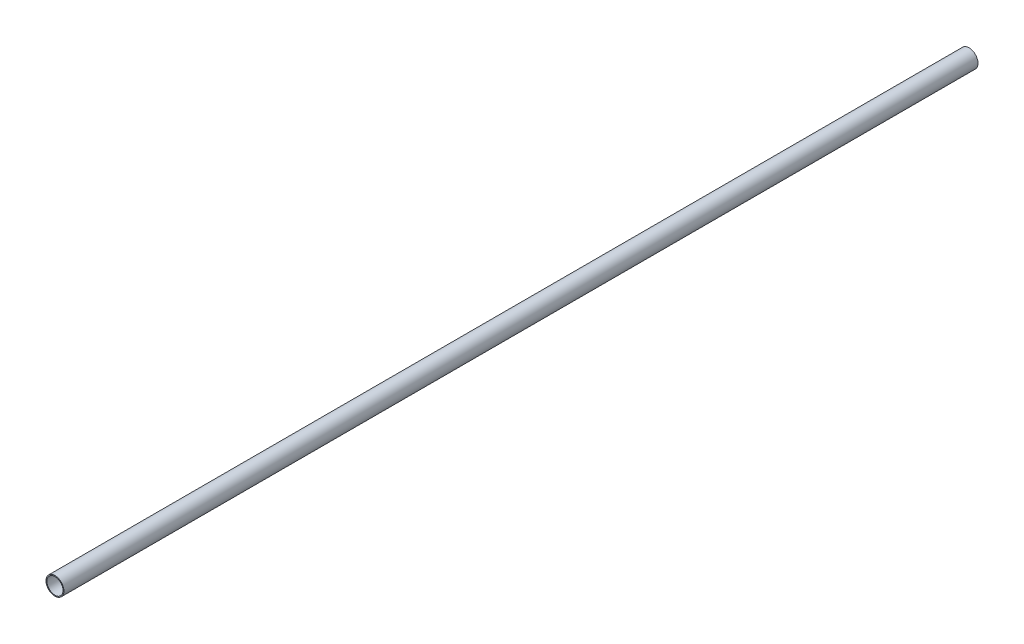
SolidWorks part; units mm, degrees
material "6061 Alloy"
ref_plane "Front Plane" through (0, 0, 0) normal (0, 0, 1) x (1, 0, 0)
ref_plane "Top Plane" through (0, 0, 0) normal (0, 1, 0) x (1, 0, 0)
ref_plane "Right Plane" through (0, 0, 0) normal (1, 0, 0) x (0, 0, -1)
sketch "Sketch1" plane through (0, 0, 0) normal (0, 0, 1) x (1, 0, 0)
  circle A0 centre (0, 0) radius 3.175
  circle A1 centre (0, 0) radius 2.8575
  dimension "D1" = 6.35
  dimension "D2" = 0.3175
extrude "Boss-Extrude1" add sketch "Sketch1" along normal blind 311.15 and the other way blind 12.7 contours A0 A1 region at (-3.0852, 0, 0)
